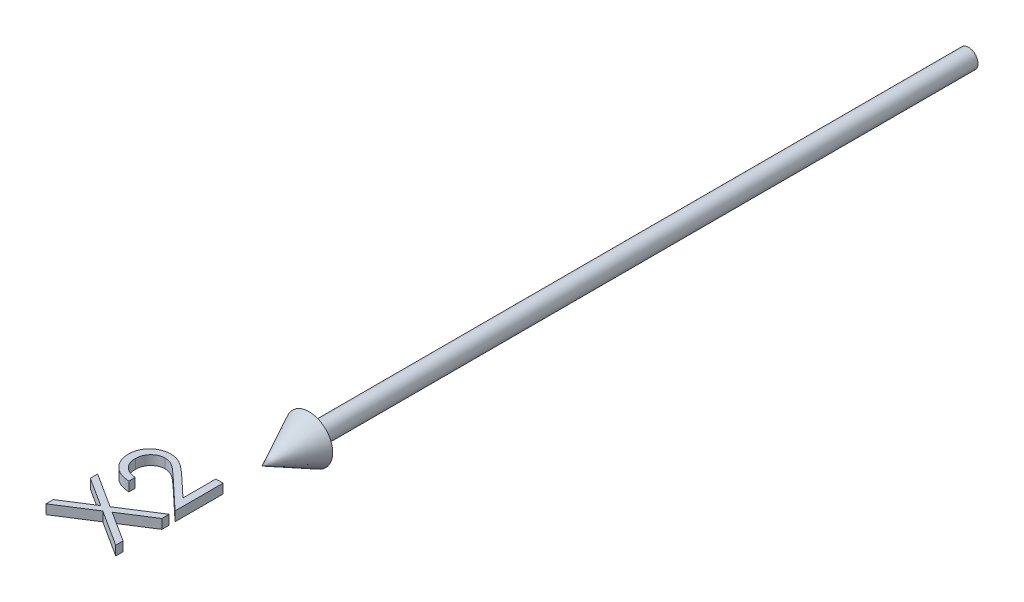
SolidWorks part; units mm, degrees
ref_plane "Front Plane" through (0, 0, 0) normal (0, 0, 1) x (1, 0, 0)
ref_plane "Top Plane" through (0, 0, 0) normal (0, 1, 0) x (1, 0, 0)
ref_plane "Right Plane" through (0, 0, 0) normal (1, 0, 0) x (0, 0, -1)
sketch "Sketch2" plane through (0, 0, 0) normal (0, 1, 0) x (1, 0, 0)
  line L0 (0, 41.95) -> (0, -114.4521) construction
  line L1 (-36.8894, 0) -> (41.4965, 0) construction
  line L2 (0, -150) -> (5, -140)
  line L3 (5, -140) -> (2, -140)
  line L4 (2, -140) -> (2, 0)
  line L5 (2, 0) -> (0, 0)
  line L6 (0, 0) -> (0, -150)
  dimension "D1" = 150
  dimension "D2" = 2
  dimension "D3" = 10
  dimension "D4" = 5
revolve "Revolve1" add sketch "Sketch2" angle 360 about L0
sketch "Sketch3" plane through (0, 0, 0) normal (0, 1, 0) x (1, 0, 0)
  line L0 (0, -157.5) -> (0, -288.4102) construction
  line L1 (-18.6107, 0) -> (18.3141, 0) construction
  text T0 "X2" font "Century Gothic" height 15
  point P3 (0, -209.1147)
  point P4 (0, -288.4102)
  point P8 (-2.5, -157.2519)
  dimension "D1" = 157.5
extrude "Boss-Extrude1" add sketch "Sketch3" against normal blind 1 and the other way blind 1 separate body
equation "\"D1@Sketch2\"=\"frame_arrow_length\""
equation "\"D2@Sketch2\"=\"frame_arrow_odA\"/2"
equation "\"D4@Sketch2\"=\"frame_arrow_head_od\""
equation "\"D3@Sketch2\"=\"frame_arrow_head_length\""
equation "\"frame_arrow_length\"=150"
equation "\"frame_arrow_head_length\"=10"
equation "\"frame_arrow_head_od\"=5"
equation "\"frame_arrow_odA\"=4"
equation "\"D1@Sketch3\"=\"frame_arrow_length\"*1.05"
